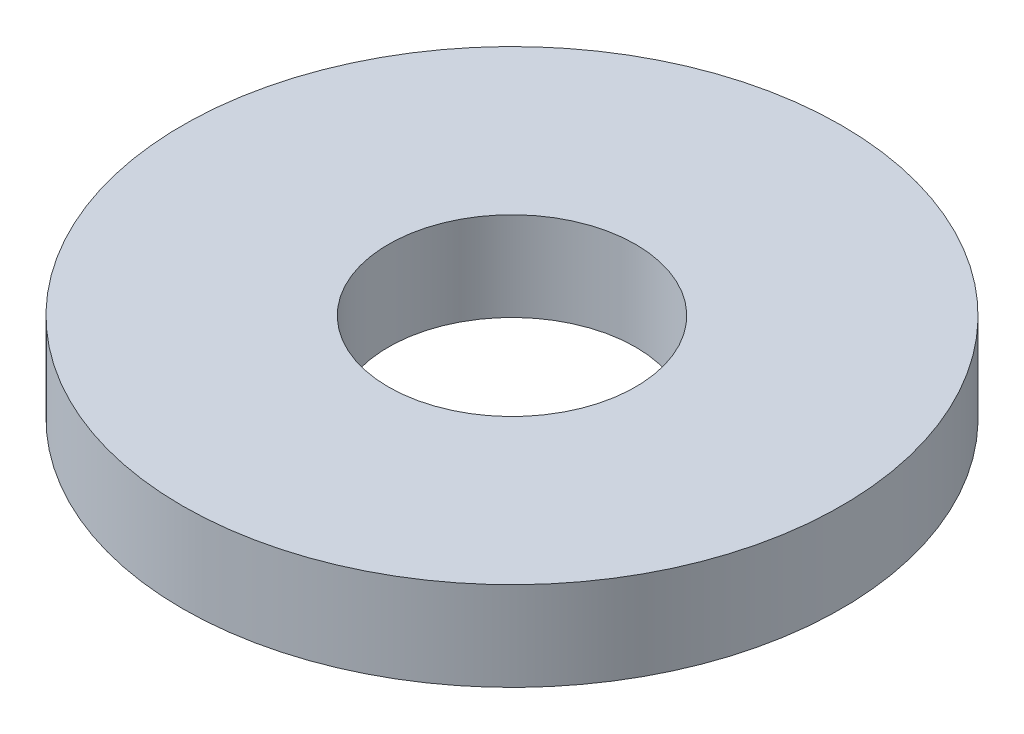
SolidWorks part; units mm, degrees
ref_plane "Front Plane" through (0, 0, 0) normal (0, 0, 1) x (1, 0, 0)
ref_plane "Top Plane" through (0, 0, 0) normal (0, 1, 0) x (1, 0, 0)
ref_plane "Right Plane" through (0, 0, 0) normal (1, 0, 0) x (0, 0, -1)
sketch "Sketch1" plane through (0, 0, 0) normal (0, 1, 0) x (1, 0, 0)
  circle A0 centre (0, 0) radius 100
  dimension "FLANGE_OD" = 200
extrude "Boss-Extrude1" add sketch "Sketch1" along normal blind 27
sketch "Sketch2" plane through (0, 0, 0) normal (0, 1, 0) x (1, 0, 0)
  circle A0 centre (0, 0) radius 37.5
  dimension "BORE_D" = 75
extrude "Cut-Extrude1" cut sketch "Sketch2" along normal through all
sketch "Sketch3" plane through (0, 27, 0) normal (0, 1, 0) x (1, 0, 0)
  circle A0 centre (0, 0) radius 24.8611 construction
  circle A1 centre (-24.8611, 0) radius 5.7413
  dimension "BOLT_D" = 11.4826
  dimension "BOLT_PCD" = 49.7221
extrude "Cut-Extrude2" cut sketch "Sketch3" against normal blind 26.6975 rebuild error yes
pattern_circular "CirPattern1" count 8 over 360 rebuild error yes
